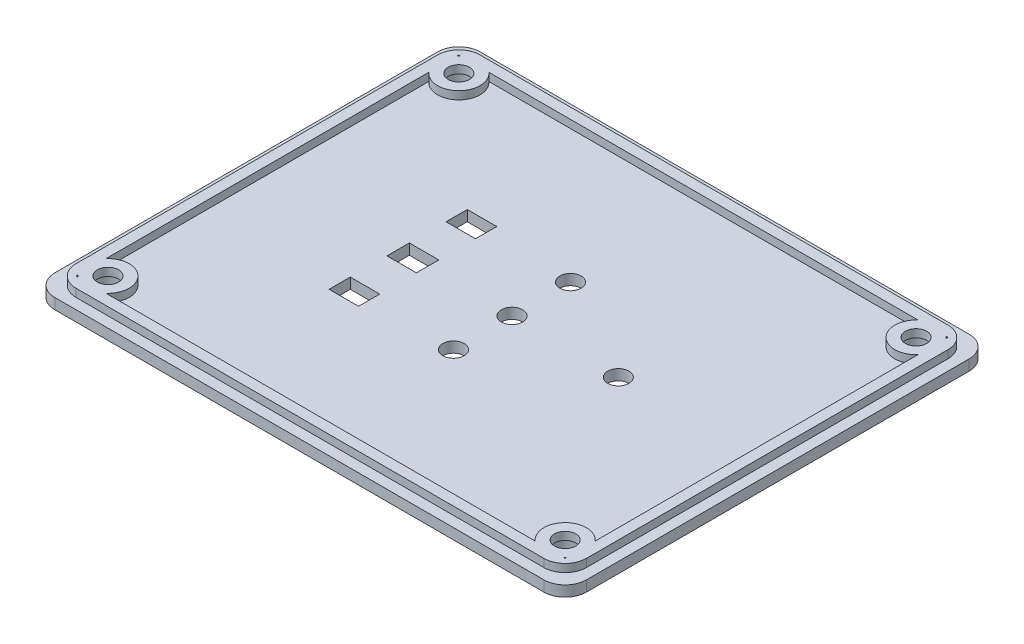
SolidWorks part; units mm, degrees
ref_plane "Front Plane" through (0, 0, 0) normal (0, 0, 1) x (1, 0, 0)
ref_plane "Top Plane" through (0, 0, 0) normal (0, 1, 0) x (1, 0, 0)
ref_plane "Right Plane" through (0, 0, 0) normal (1, 0, 0) x (0, 0, -1)
sketch "Sketch1" plane through (0, 0, 0) normal (0, 1, 0) x (1, 0, 0)
  line L1 (-50, 40) -> (50, 40)
  line L2 (-50, 40) -> (-50, -40)
  line L3 (-50, -40) -> (50, -40)
  line L4 (50, 40) -> (50, -40)
  line L5 (-50, 40) -> (50, -40) construction
  line L6 (-50, -40) -> (50, 40) construction
  point P0 (0, 0)
  dimension "D1" = 80
  dimension "D2" = 100
extrude "Boss-Extrude2" add sketch "Sketch1" along normal blind 2 contours L3 L4 L1 L2
sketch "Sketch3" plane through (0, 2, 0) normal (0, 1, 0) x (1, 0, 0)
  line L1 (-48, 38) -> (48, 38)
  line L2 (-48, 38) -> (-48, -38)
  line L3 (-48, -38) -> (48, -38)
  line L4 (48, 38) -> (48, -38)
  line L5 (-48, 38) -> (48, -38) construction
  line L6 (-48, -38) -> (48, 38) construction
  point P0 (0, 0)
  dimension "D1" = 76
  dimension "D2" = 96
extrude "Boss-Extrude3" add sketch "Sketch3" along normal blind 1.5
sketch "Sketch5" plane through (0, 3.5, 0) normal (0, 1, 0) x (1, 0, 0)
  line L0 (-48, -38) -> (48, -38) construction
  line L1 (-48, 38) -> (-48, -38) construction
  line L2 (48, 38) -> (-48, 38) construction
  line L3 (48, -38) -> (48, 38) construction
  circle A0 centre (-43, -33) radius 2
  circle A1 centre (-43, 33) radius 2
  circle A2 centre (43, -33) radius 2
  circle A3 centre (43, 33) radius 2
  point P0 (-43, 33)
  point P1 (-43, -33)
  point P2 (43, -33)
  point P3 (43, 33)
  dimension "D1" = 5
  dimension "D2" = 5
  dimension "D3" = 5
  dimension "D4" = 5
  dimension "D5" = 5
  dimension "D6" = 5
  dimension "D7" = 5
  dimension "D8" = 5
extrude "Cut-Extrude1" cut sketch "Sketch5" against normal blind 35 contours A3 | A2 | A1 | A0
shell "Shell1" thickness 2 removed face at (43, 3.5, 35)
fillet "Fillet1" radius 4 1 edges at (-48, 2.75, 38)
fillet "Fillet2" radius 4 3 edges at (48, 2.75, 38) (48, 2.75, -38) (-48, 2.75, -38)
fillet "Fillet3" radius 4 4 edges at (50, 1, 40) (50, 1, -40) (-50, 1, -40) (-50, 1, 40)
sketch "Sketch10" plane through (0, 0, 0) normal (0, -1, 0) x (1, 0, 0)
  line L0 (50, -36) -> (50, 36) construction
  line L2 (-21.5294, -9.1199) -> (-15.9928, -9.1199)
  line L3 (-21.5294, -9.1199) -> (-21.5294, -13.1199)
  line L4 (-21.5294, -13.1199) -> (-15.9928, -13.1199)
  line L5 (-15.9928, -9.1199) -> (-15.9928, -13.1199)
  line L6 (-21.5294, -9.1199) -> (-15.9928, -13.1199) construction
  line L7 (-21.5294, -13.1199) -> (-15.9928, -9.1199) construction
  line L8 (-21.5294, 1.9843) -> (-15.9928, 1.9843)
  line L9 (-21.5294, 1.9843) -> (-21.5294, -2.2241)
  line L10 (-21.5294, -2.2241) -> (-15.9928, -2.2241)
  line L11 (-15.9928, 1.9843) -> (-15.9928, -2.2241)
  line L12 (-21.5294, 1.9843) -> (-15.9928, -2.2241) construction
  line L13 (-21.5294, -2.2241) -> (-15.9928, 1.9843) construction
  line L14 (-21.5294, 12.8713) -> (-15.9928, 12.8713)
  line L15 (-21.5294, 12.8713) -> (-21.5294, 8.8889)
  line L16 (-21.5294, 8.8889) -> (-15.9928, 8.8889)
  line L17 (-15.9928, 12.8713) -> (-15.9928, 8.8889)
  line L18 (-21.5294, 12.8713) -> (-15.9928, 8.8889) construction
  line L19 (-21.5294, 8.8889) -> (-15.9928, 12.8713) construction
  circle A0 centre (0, -11) radius 2
  circle A1 centre (0, 0) radius 2
  circle A3 centre (0, 11) radius 2
  circle A4 centre (20, 0) radius 2
  point P0 (0, -11)
  point P1 (0, 0)
  point P2 (0, 11)
  point P6 (50, 0)
  point P13 (-18.7611, -11.1199)
  point P20 (-18.7611, -0.1199)
  point P25 (-18.7611, 10.8801)
  dimension "D4" = 20
  dimension "D1" = 50
  dimension "D2" = 11
  dimension "D3" = 11
  dimension "D5" = 11
  dimension "D6" = 11
extrude "Cut-Extrude2" cut sketch "Sketch10" against normal blind 5 contours A4 | A3 | A1 | A0 | L3 L4 L5 L2 | L9 L10 L11 L8 | L14 L17 L16 L15
sketch "Sketch11" plane through (0, 0, 0) normal (0, -1, 0) x (1, 0, 0)
  circle A0 centre (43, 33) radius 2.6
  circle A1 centre (43, -33) radius 2.6
  circle A2 centre (-43, -33) radius 2.6
  circle A3 centre (-43, 33) radius 2.6
extrude "Cut-Extrude3" cut sketch "Sketch11" against normal blind 2
